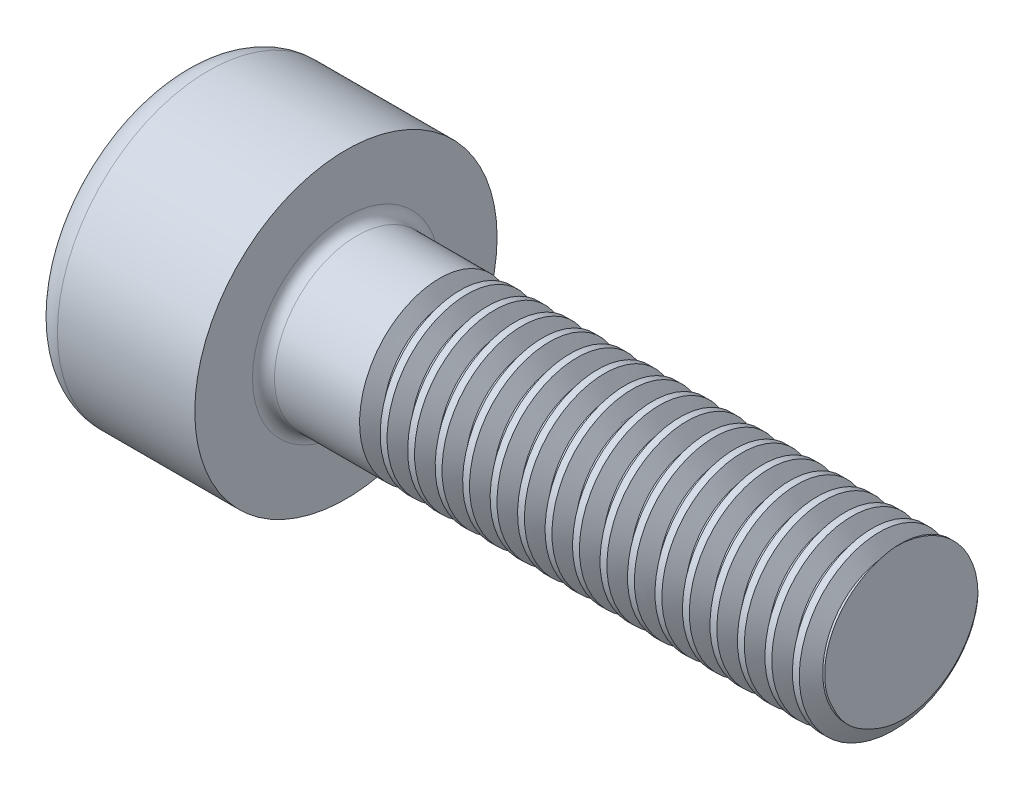
SolidWorks part; units mm, degrees
ref_plane "Спереди" through (0, 0, 0) normal (0, 0, 1) x (1, 0, 0)
ref_plane "Сверху" through (0, 0, 0) normal (0, 1, 0) x (1, 0, 0)
ref_plane "Справа" through (0, 0, 0) normal (1, 0, 0) x (0, 0, -1)
sketch "Эскиз1" plane through (0, 0, 0) normal (0, 0, 1) x (1, 0, 0)
  line L0 (22.1989, 0) -> (13, 0) construction
  line L1 (0, 16.1035) -> (0, -19.7496) construction
  line L2 (0, 0) -> (13, 0)
  line L3 (0, 0) -> (0, 2.75)
  line L4 (0, 2.75) -> (3, 2.75)
  line L5 (3, 2.75) -> (3, 1.5)
  line L6 (3, 1.5) -> (13, 1.5)
  line L7 (13, 1.5) -> (13, 0)
  point P2 (0, 0)
  point P7 (0, 0)
  point P8 (6.5, 0)
  point P13 (0, 0)
  point P14 (11.0203, 0)
  point P15 (0, 0)
  point P16 (22.1989, 0)
  dimension "D1" = 5.5
  dimension "D2" = 3
  dimension "D3" = 10
  dimension "D4" = 3
revolve "Повернуть1" add sketch "Эскиз1" angle 360 about L0
thread "Резьба1" pitch 0.5 method cut profile "Профиль резьбы2" start angle 0, offset 1.5, length 0, pitch 0.5, diameter 3
ref_plane "Плоскость2" through (4.5, 0, -1.5) normal (0, 1, 0) x (0, 0, 1)
sketch "Профиль резьбы2" plane through (4.5, 0, -1.5) normal (0, 1, 0) x (0, 0, 1)
  line L0 (0, 0) -> (0, 0.5) construction
  line L1 (0, 0) -> (0.2706, 0.1562)
  line L2 (0.2706, 0.1562) -> (0.2706, 0.2187)
  line L3 (0.2706, 0.2187) -> (0, 0.375)
  line L4 (0.2706, 0.1875) -> (0, 0.1875) construction
  line L11 (0, 0) -> (0, 0.375)
  point P2 (0, 0)
  dimension "Pitch" = 0.5
  dimension "Profile_Angle" = 60
  dimension "Profile_Land" = 0.0625
  dimension "Profile_Height" = 0.2706
sketch "Эскиз6" plane through (0, 0, 0) normal (-1, 0, 0) x (0, 0, 1)
  line L0 (0, 0) -> (-5.0338, 0) construction
  line L1 (0, 0) -> (0, 5.5177) construction
  line L3 (-1.435, 0) -> (-0.7175, -1.2427)
  line L4 (-0.7175, -1.2427) -> (0.7175, -1.2427)
  line L5 (0.7175, -1.2427) -> (1.435, 0)
  line L6 (1.435, 0) -> (0.7175, 1.2427)
  line L7 (0.7175, 1.2427) -> (-0.7175, 1.2427)
  line L8 (-0.7175, 1.2427) -> (-1.435, 0)
  point P3 (0, 0)
  dimension "D1" = 2.4855
  dimension "D2" = 2.87
extrude "Вырез-Вытянуть1" cut sketch "Эскиз6" against normal blind 2 contours L3 L4 L5 L6 L7 L8
extrude "Вырез-Вытянуть2" cut sketch "Эскиз6<3>" against normal blind 2 draft 60 from offset 2 offset against normal yes
sketch "Эскиз6<3>" plane through (0, 0, 0) normal (-1, 0, 0) x (0, 0, 1) same geometry as "Эскиз6"
fillet "Скругление2" radius 0.5 1 edges at (0, 0, -2.75)
fillet "Скругление3" radius 0.2 1 edges at (3, 0, -1.5)
